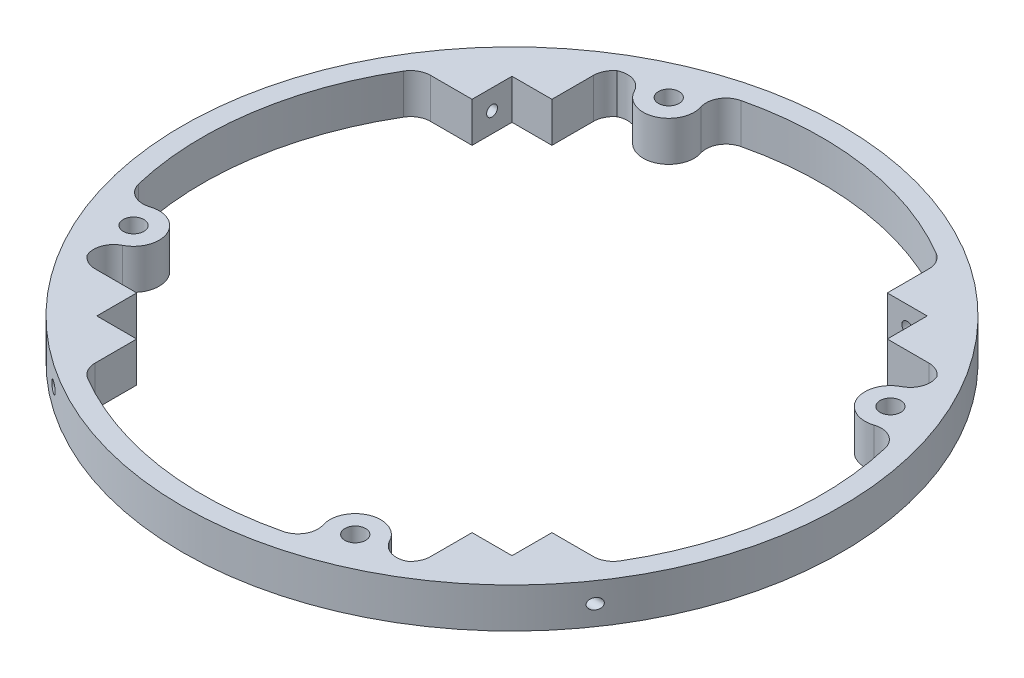
SolidWorks part; units mm, degrees
ref_plane "Front Plane" through (0, 0, 0) normal (0, 0, 1) x (1, 0, 0)
ref_plane "Top Plane" through (0, 0, 0) normal (0, 1, 0) x (1, 0, 0)
ref_plane "Right Plane" through (0, 0, 0) normal (1, 0, 0) x (0, 0, -1)
sketch "Sketch1" plane through (0, 0, 0) normal (0, 1, 0) x (1, 0, 0)
  line L0 (0, 0) -> (0, 84.2831) construction
  line L1 (-52, 52) -> (52, 52) construction
  line L2 (-52, 52) -> (-52, -52) construction
  line L3 (-52, -52) -> (52, -52) construction
  line L4 (52, 52) -> (52, -52) construction
  line L5 (0, 0) -> (-99.9306, 0) construction
  line L6 (0, 0) -> (-52, 52) construction
  line L7 (0, 0) -> (-31.8699, 76.9407) construction
  line L8 (-42, 52) -> (-52, 52)
  line L9 (-52, 52) -> (-52, 42)
  line L10 (-52, 42) -> (-65.192, 42)
  line L11 (-42, 52) -> (-42, 65.192)
  line L12 (-35.4887, 68.9533) -> (-33.6765, 64.5783)
  line L13 (-23.663, 73.8516) -> (-21.8509, 69.4766)
  line L14 (42, 52) -> (42, 65.192)
  line L15 (52, 52) -> (42, 52)
  line L16 (52, 42) -> (52, 52)
  line L17 (52, 42) -> (65.192, 42)
  line L18 (68.9533, 35.4887) -> (64.5783, 33.6765)
  line L19 (73.8516, 23.663) -> (69.4766, 21.8509)
  line L20 (52, -42) -> (65.192, -42)
  line L21 (52, -52) -> (52, -42)
  line L22 (42, -52) -> (52, -52)
  line L23 (42, -52) -> (42, -65.192)
  line L24 (35.4887, -68.9533) -> (33.6765, -64.5783)
  line L25 (23.663, -73.8516) -> (21.8509, -69.4766)
  line L26 (-42, -52) -> (-42, -65.192)
  line L27 (-52, -52) -> (-42, -52)
  line L28 (-52, -42) -> (-52, -52)
  line L29 (-52, -42) -> (-65.192, -42)
  line L30 (-68.9533, -35.4887) -> (-64.5783, -33.6765)
  line L31 (-73.8516, -23.663) -> (-69.4766, -21.8509)
  circle A0 centre (0, 0) radius 82.55
  arc A1 (-65.192, 42) -> (-77.55, 0) centre (0, 0) ccw
  arc A2 (-42, 65.192) -> (-35.4887, 68.9533) centre (0, 0) cw
  arc A3 (-33.6765, 64.5783) -> (-21.8509, 69.4766) centre (-27.7637, 67.0275) ccw
  arc A4 (0, 77.55) -> (-23.663, 73.8516) centre (0, 0) ccw
  arc A5 (42, 65.192) -> (0, 77.55) centre (0, 0) ccw
  arc A6 (65.192, 42) -> (68.9533, 35.4887) centre (0, 0) cw
  arc A7 (64.5783, 33.6765) -> (69.4766, 21.8509) centre (67.0275, 27.7637) ccw
  arc A8 (77.55, 0) -> (73.8516, 23.663) centre (0, 0) ccw
  arc A9 (65.192, -42) -> (77.55, 0) centre (0, 0) ccw
  arc A10 (42, -65.192) -> (35.4887, -68.9533) centre (0, 0) cw
  arc A11 (33.6765, -64.5783) -> (21.8509, -69.4766) centre (27.7637, -67.0275) ccw
  arc A12 (0, -77.55) -> (23.663, -73.8516) centre (0, 0) ccw
  arc A13 (-42, -65.192) -> (0, -77.55) centre (0, 0) ccw
  arc A14 (-65.192, -42) -> (-68.9533, -35.4887) centre (0, 0) cw
  arc A15 (-64.5783, -33.6765) -> (-69.4766, -21.8509) centre (-67.0275, -27.7637) ccw
  arc A16 (-77.55, 0) -> (-73.8516, -23.663) centre (0, 0) ccw
  point P21 (-22.7569, 71.6641)
  point P61 (0, 0)
  dimension "D1" = 165.1
  dimension "D2" = 104
  dimension "D3" = 22.5
  dimension "D4" = 5
  dimension "D5" = 72.55
  dimension "D6" = 12.8
  dimension "D7" = 10
  dimension "D8" = 4
extrude "Boss-Extrude1" add sketch "Sketch1" along normal blind 10
fillet "Fillet1" radius 5 16 edges at (-73.8516, 5, 23.663) (-68.9533, 5, 35.4887) (-42, 5, 65.192) (-65.192, 5, 42) (23.663, 5, 73.8516) (35.4887, 5, 68.9533) (42, 5, 65.192) (65.192, 5, 42) (73.8516, 5, -23.663) (68.9533, 5, -35.4887) (65.192, 5, -42) (42, 5, -65.192) (-35.4887, 5, -68.9533) (-23.663, 5, -73.8516) (-42, 5, -65.192) (-65.192, 5, -42)
hole_wizard "#6 (0.204) Diameter Hole1" positions "Sketch4" profile "Sketch3" hole size "#6" standard "ANSI Inch" end condition through all
sketch "Sketch4" plane through (0, 10, 0) normal (0, 1, 0) x (1, 0, 0)
  point P0 (67.0275, 27.7637)
sketch "Sketch3" plane through (67.0275, 10, -27.7637) normal (1, 0, 0) x (0, 0, 1)
  line L0 (0, 0) -> (0, 10)
  line L1 (0, 10) -> (2.5908, 10)
  line L2 (2.5908, 10) -> (2.5908, 0)
  line L5 (2.5908, 0) -> (0, 0)
  line L11 (0, -6.35) -> (0, 107.95) construction
  dimension "Thru Hole Dia." = 5.1816
  dimension "Thru Hole Depth" = 10
hole_wizard "#6-32 Tapped Hole2" positions "Sketch8" profile "Sketch9" tap size "#6-32" standard "ANSI Inch" end condition through all
sketch "Sketch8" plane through (0, 0, -52) normal (0, 0, 1) x (1, 0, 0)
  line L0 (52, 0) -> (42, 10)
  point P0 (47, 5)
  point P10 (47, 5)
sketch "Sketch9" plane through (47, 5, -52) normal (1, 0, 0) x (0, -1, 0)
  line L0 (0, 0) -> (0, 30.55)
  line L1 (0, 30.55) -> (1.3525, 30.55)
  line L2 (1.3525, 30.55) -> (1.3525, 0)
  line L5 (1.3525, 0) -> (0, 0)
  line L11 (0, -6.35) -> (0, 107.95) construction
  dimension "Thru Tap Drill Dia." = 2.7051
  dimension "Thru Tap Drill Depth" = 30.55
cosmetic thread "Hole Thread2" parameters "D2"=3.5052
ref_axis "Axis1" through (0, 10.5, 0) along (0, -1, 0)
pattern_circular "CirPattern1" count 4 over 360 about axis through (0, 10.5, 0) along (0, -1, 0) of "#6 (0.204) Diameter Hole1", "#6-32 Tapped Hole2"
equation "\"TubeDiameter\" = 6.500in"
equation "\"D1@Sketch1\"=\"TubeDiameter\""
equation "\"D5@Sketch1\"=\"TubeDiameter\"/2-10mm"
